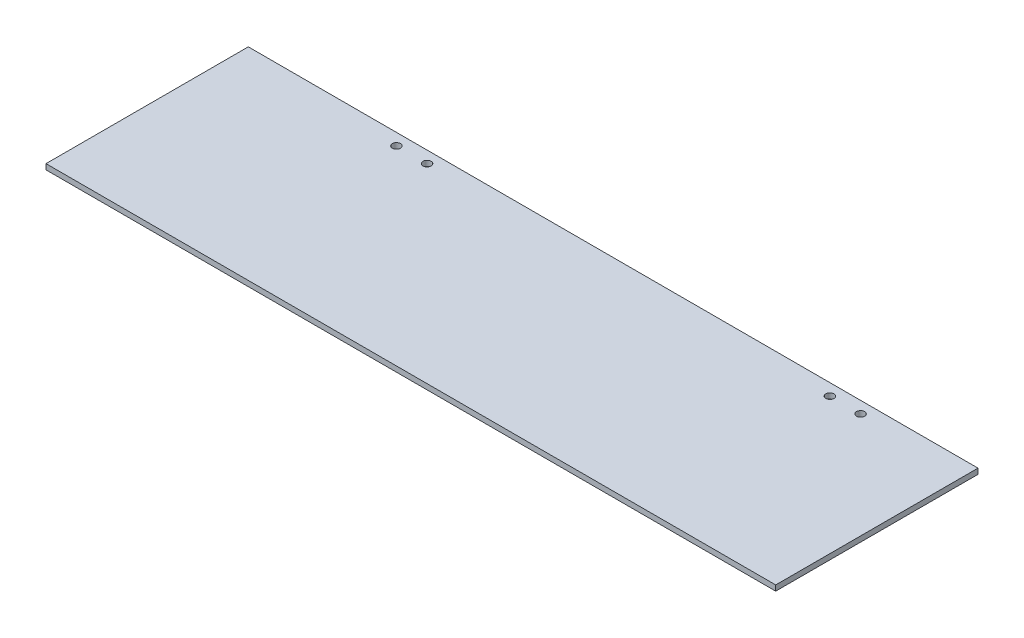
SolidWorks part; units mm, degrees
ref_plane "Front Plane" through (0, 0, 0) normal (0, 0, 1) x (1, 0, 0)
ref_plane "Top Plane" through (0, 0, 0) normal (0, 1, 0) x (1, 0, 0)
ref_plane "Right Plane" through (0, 0, 0) normal (1, 0, 0) x (0, 0, -1)
sketch "Sketch1" plane through (0, 0, 0) normal (0, 1, 0) x (1, 0, 0)
  line L1 (-202, -56) -> (202, -56)
  line L2 (-202, -56) -> (-202, 56)
  line L3 (-202, 56) -> (202, 56)
  line L4 (202, -56) -> (202, 56)
  line L5 (-202, -56) -> (202, 56) construction
  line L6 (-202, 56) -> (202, -56) construction
  point P0 (0, 0)
  dimension "D1" = 404
  dimension "D2" = 112
extrude "Boss-Extrude1" add sketch "Sketch1" along normal blind 3
hole_wizard "M4 Clearance Hole1" positions "Sketch2" profile "Sketch3" hole size "M4" standard "ANSI Metric" end condition through all
sketch "Sketch2" plane through (0, 3, 0) normal (0, 1, 0) x (1, 0, 0)
  line L0 (126.5, 49.5) -> (143.5, 49.5)
  line L2 (202, 56) -> (-202, 56) construction
  line L3 (202, -56) -> (202, 56) construction
  point P1 (126.5, 49.5)
  point P2 (143.5, 49.5)
  dimension "D1" = 6.5
  dimension "D2" = 17
  dimension "D3" = 58.5
sketch "Sketch3" plane through (126.5, 3, -49.5) normal (1, 0, 0) x (0, 0, 1)
  line L0 (0, 0) -> (0, 3)
  line L1 (0, 3) -> (2.25, 3)
  line L2 (2.25, 3) -> (2.25, 0)
  line L5 (2.25, 0) -> (0, 0)
  line L11 (0, -6.35) -> (0, 107.95) construction
  dimension "Thru Hole Dia." = 4.5
  dimension "Thru Hole Depth" = 3
pattern_linear "LPattern1" count 2 spacing 240 along (-1, 0, 0) of "M4 Clearance Hole1"
